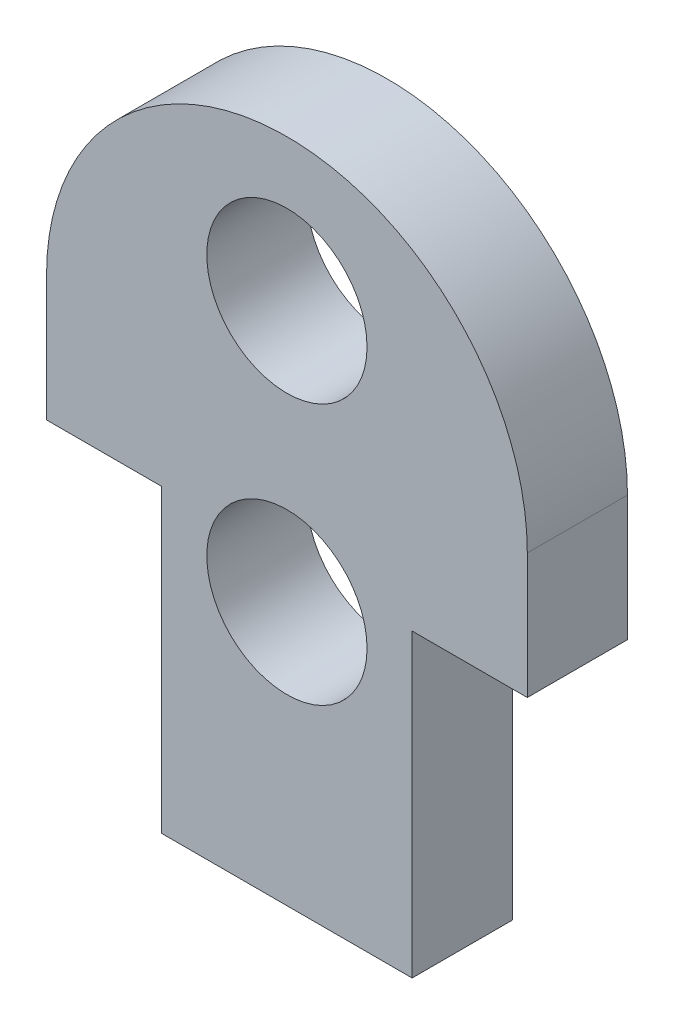
SolidWorks part; units mm, degrees
ref_plane "Front Plane" through (0, 0, 0) normal (0, 0, 1) x (1, 0, 0)
ref_plane "Top Plane" through (0, 0, 0) normal (0, 1, 0) x (1, 0, 0)
ref_plane "Right Plane" through (0, 0, 0) normal (1, 0, 0) x (0, 0, -1)
sketch "Sketch1" plane through (0, 0, 0) normal (0, 0, 1) x (1, 0, 0)
  line L0 (0, 0) -> (10, 0)
  line L1 (0, 0) -> (0, 4)
  line L2 (0, 4) -> (-2.5, 4)
  line L3 (3.3546, 18.0712) -> (6.6454, 18.0712) construction
  line L4 (-2.5, 4) -> (-2.5, 8)
  line L5 (-2.5, 8) -> (0, 8)
  line L6 (0, 8) -> (0, 12)
  line L7 (5, 0) -> (5, 27) construction
  line L8 (10, 0) -> (10, 4)
  line L9 (10, 4) -> (12.5, 4)
  line L10 (12.5, 4) -> (12.5, 8)
  line L11 (12.5, 8) -> (10, 8)
  line L12 (3.3546, 23.7712) -> (1.7091, 20.9212) construction
  line L13 (8.2909, 10.5) -> (6.6454, 13.35) construction
  line L14 (6.6454, 13.35) -> (3.3546, 13.35) construction
  line L15 (3.3546, 13.35) -> (1.7091, 10.5) construction
  line L16 (1.7091, 10.5) -> (3.3546, 7.65) construction
  line L17 (3.3546, 7.65) -> (6.6454, 7.65) construction
  line L18 (6.6454, 7.65) -> (8.2909, 10.5) construction
  line L19 (1.7091, 20.9212) -> (3.3546, 18.0712) construction
  line L20 (0, 12) -> (-4.6, 12)
  line L21 (10, 8) -> (10, 12)
  line L22 (6.6454, 18.0712) -> (8.2909, 20.9212) construction
  line L23 (8.2909, 20.9212) -> (6.6454, 23.7712) construction
  line L24 (6.6454, 23.7712) -> (3.3546, 23.7712) construction
  line L25 (10, 12) -> (14.6, 12)
  line L26 (-4.6, 12) -> (-4.6, 17)
  line L27 (14.6, 12) -> (14.6, 17)
  line L28 (3.3546, 23.7712) -> (6.6454, 18.0712) construction
  line L29 (6.6454, 23.7712) -> (3.3546, 18.0712) construction
  line L30 (3.3546, 13.35) -> (6.6454, 7.65) construction
  line L31 (6.6454, 13.35) -> (3.3546, 7.65) construction
  circle A0 centre (5, 20.9212) radius 3 construction
  arc A1 (14.6, 17) -> (-4.6, 17) centre (5, 17) ccw
  circle A2 centre (5, 10.5) radius 3 construction
  dimension "D3" = 6
  dimension "D5" = 2.5
  dimension "D9" = 4
  dimension "D10" = 4
  dimension "D12" = 2.5
  dimension "D8" = 4.6
  dimension "D2" = 5.7
extrude "Boss-Extrude1" add sketch "Sketch1" along normal blind 4
sketch "Sketch2" plane through (0, 0, 4) normal (0, 0, 1) x (1, 0, 0)
  line L0 (-2.5, 8) -> (0, 8)
  line L1 (0, 8) -> (0, 4)
  line L2 (0, 4) -> (-2.5, 4)
  line L3 (-2.5, 4) -> (-2.5, 8)
  line L4 (10, 8) -> (12.5, 8)
  line L5 (12.5, 8) -> (12.5, 4)
  line L6 (12.5, 4) -> (10, 4)
  line L7 (10, 4) -> (10, 8)
extrude "Cut-Extrude1" cut sketch "Sketch2" against normal up to surface (4 mm away) up to face at (5, 8.725, 0)
sketch "Sketch3" plane through (0, 0, 0) normal (0, 0, 1) x (1, 0, 0)
  circle A0 centre (5, 20.9212) radius 3.2
  circle A2 centre (5, 10.5) radius 3.2
  dimension "D1" = 6.4
  dimension "D2" = 10.5
  dimension "D3" = 5
  dimension "D4" = 10.4212
extrude "Cut-Extrude2" cut sketch "Sketch3" along normal through all
equation "\"D8@Sketch1\"= 5 - \"tol2@parametersSketch@prostheticParameters.SLDPRT\""
equation "\"D1@Sketch3\"= 6 + \"tol1@parametersSketch@prostheticParameters.SLDPRT\""
